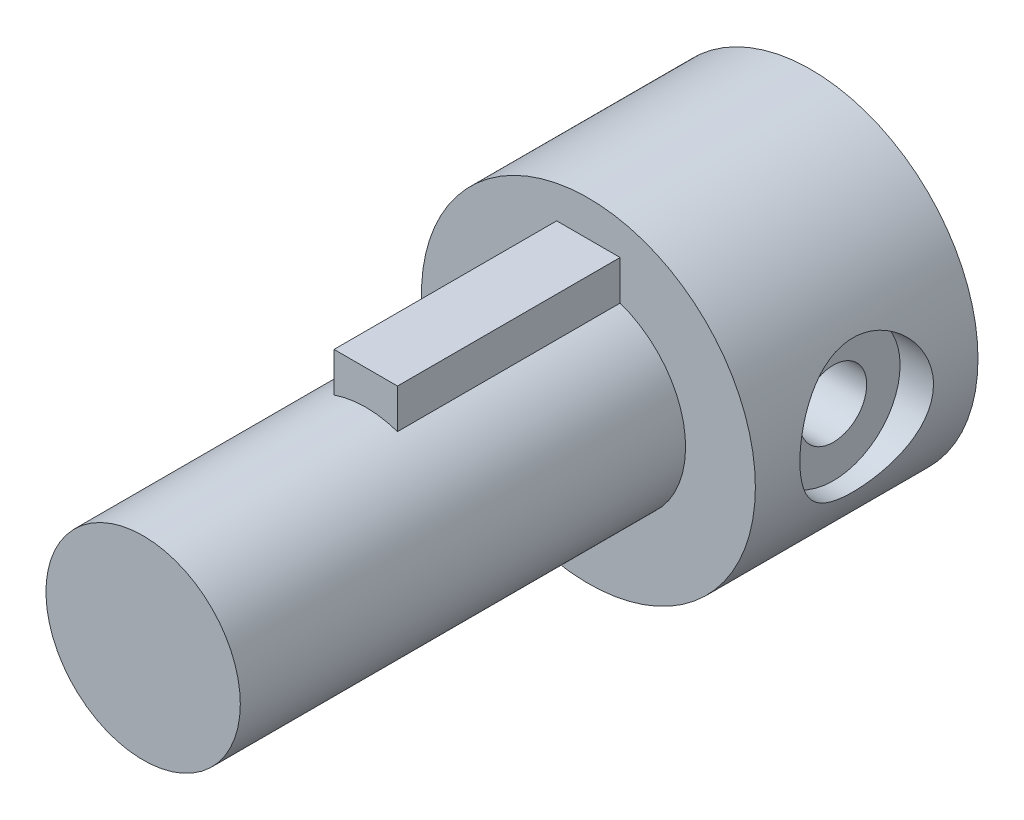
SolidWorks part; units mm, degrees
ref_plane "Front Plane" through (0, 0, 0) normal (0, 0, 1) x (1, 0, 0)
ref_plane "Top Plane" through (0, 0, 0) normal (0, 1, 0) x (1, 0, 0)
ref_plane "Right Plane" through (0, 0, 0) normal (1, 0, 0) x (0, 0, -1)
sketch "Sketch2" plane through (0, 0, 0) normal (0, 0, 1) x (1, 0, 0)
  circle A0 centre (0, 0) radius 7.5
  circle A1 centre (0, 0) radius 3
  dimension "D1" = 15
extrude "Boss-Extrude1" add sketch "Sketch2" along normal blind 10
sketch "Sketch3" plane through (0, 0, 0) normal (1, 0, 0) x (0, -1, 0)
  line L0 (-7.5, -5) -> (7.5, -5) construction
  line L1 (-7.5, 0) -> (-7.5, -10) construction
  line L2 (7.5, -10) -> (7.5, 0) construction
  circle A0 centre (0, -5) radius 1.5
  circle A1 centre (0, -5) radius 3
  circle A2 centre (0, -5) radius 4.1216
  dimension "D1" = 3
extrude "Cut-Extrude1" cut sketch "Sketch3" against normal through all both and the other way through all contours A0 L0 | L0 A0 | A1 L0 A0 | L0 A1 A0 region at (0, 0, 3.4329) region at (0, 0, 5.6366) region at (0, 0, 4.3634) region at (0, -2.25, 5.0671)
extrude "Boss-Extrude6" add sketch "Sketch3<5>" along normal mid plane 12 contours L0 A2 A1 | L0 A1 A0 | A2 L0 A1 | A1 L0 A0 region at (0, 0, 3.4329) region at (0, -2.25, 5.0671) region at (0, 0, 1.9078) region at (0, -3.5608, 5.0922)
sketch "Sketch3<5>" plane through (0, 0, 0) normal (1, 0, 0) x (0, -1, 0) same geometry as "Sketch3"
sketch "Sketch4" plane through (0, 0, 10) normal (0, 0, 1) x (1, 0, 0)
  line L0 (0, 7.5) -> (0, 5.9) construction
  line L1 (-1.425, -5.9) -> (1.425, -5.9)
  line L2 (-1.425, -5.9) -> (-1.425, 5.9)
  line L3 (-1.425, 5.9) -> (1.425, 5.9)
  line L4 (1.425, -5.9) -> (1.425, 5.9)
  line L5 (-1.425, -5.9) -> (1.425, 5.9) construction
  line L6 (-1.425, 5.9) -> (1.425, -5.9) construction
  circle A0 centre (0, 0) radius 4.365
  circle A1 centre (0, 0) radius 7.5 construction
  circle M4 centre (0, 0) radius 3
  dimension "D1" = 8.73
  dimension "D3" = 15
  dimension "D2" = 1.6
  dimension "D4" = 2.85
extrude "Boss-Extrude7" add sketch "Sketch4" along normal blind 10 contours L2 A0 M4 | L4 A0 L2 M4 | A0 L4 L3 L2 | L4 A0 M4 | L2 A0 L4 M4 | L2 M4 | L4 L2 M4 | L4 M4 region at (-4.2774, 0, 10) region at (0, -3.5824, 10) region at (1.5126, -3.3829, 10) region at (-2.0717, 0, 10) region at (0, 0, 10) region at (0, 3.5824, 10) region at (0, 5.0915, 10) region at (2.0717, 0, 10)
sketch "Sketch5" plane through (0, 0, 0) normal (0, 0, -1) x (-1, 0, 0)
  circle A0 centre (0, 0) radius 3
extrude "Cut-Extrude3" cut sketch "Sketch5" against normal blind 10
sketch "Sketch6" plane through (0, 0, 20) normal (0, 0, 1) x (1, 0, 0)
  circle A0 centre (0, 0) radius 4.365
  arc A1 (-1.425, 4.1258) -> (1.425, 4.1258) centre (0, 0) ccw construction
  arc A2 (-1.425, 4.1258) -> (1.425, 4.1258) centre (0, 0) ccw construction
extrude "Boss-Extrude8" add sketch "Sketch6" along normal blind 10
